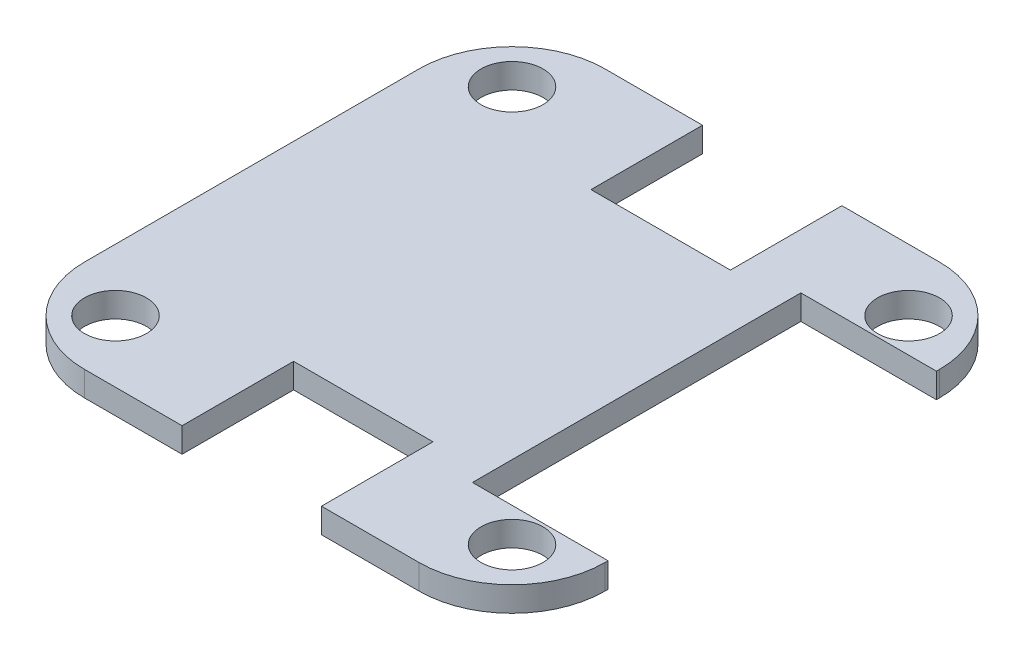
SolidWorks part; units mm, degrees
ref_plane "Front Plane" through (0, 0, 0) normal (0, 0, 1) x (1, 0, 0)
ref_plane "Top Plane" through (0, 0, 0) normal (0, 1, 0) x (1, 0, 0)
ref_plane "Right Plane" through (0, 0, 0) normal (1, 0, 0) x (0, 0, -1)
sketch "Layer1" plane through (0, 0, 0) normal (0, 1, 0) x (1, 0, 0)
  line L0 (11.25, 42) -> (27, 42)
  line L1 (-27, -42) -> (-11.25, -42)
  line L2 (-42, -27) -> (-42, 27)
  line L3 (-27, 42) -> (-11.25, 42)
  line L4 (42, -27) -> (42, 27)
  line L5 (-42, -42) -> (42, 42) construction
  line L6 (-42, 42) -> (42, -42) construction
  line L8 (-11.25, 42) -> (-11.25, 24)
  line L9 (-11.25, 24) -> (11.25, 24)
  line L10 (11.25, 42) -> (11.25, 24)
  line L12 (-11.25, -42) -> (-11.25, -24)
  line L13 (-11.25, -24) -> (11.25, -24)
  line L14 (11.25, -42) -> (11.25, -24)
  line L15 (11.25, -42) -> (27, -42)
  line L18 (-42, -21.5) -> (-42, 21.5)
  arc A0 (27, -42) -> (42, -27) centre (27, -27) ccw
  arc A1 (27, 42) -> (42, 27) centre (27, 27) cw
  arc A2 (-27, -42) -> (-42, -27) centre (-27, -27) cw
  arc A3 (-42, 27) -> (-27, 42) centre (-27, 27) cw
  point P0 (0, 0)
  point P30 (21.7219, 0)
  dimension "D9" = 15
  dimension "D1" = 84
  dimension "D2" = 84
  dimension "D3" = 18
  dimension "D4" = 22.5
  dimension "D5" = 18
  dimension "D6" = 22.5
  dimension "D7" = 30.75
  dimension "D8" = 30.75
  dimension "D10" = 43
extrude "Boss-Extrude1" add sketch "Layer1" along normal blind 4 contours A3 L2 A2 L1 L12 L13 L14 L15 A0 L4 A1 L0 L10 L9 L8 L3 | L2 region at (0, 0, 0)
sketch "Sketch4" plane through (0, 4, 0) normal (0, 1, 0) x (1, 0, 0)
  line L0 (11.25, 42) -> (27, 42) construction
  line L1 (20.12, -26.5) -> (42, -26.5)
  line L2 (20.12, -26.5) -> (20.12, 26.5)
  line L3 (20.12, 26.5) -> (42, 26.5)
  line L4 (42, -26.5) -> (42, 26.5)
  line L5 (20.12, -26.5) -> (42, 26.5) construction
  line L6 (20.12, 26.5) -> (42, -26.5) construction
  line L7 (42, -27) -> (42, 27) construction
  line L8 (-42, -27) -> (-42, 27) construction
  line L13 (-27, 42) -> (-11.25, 42) construction
  line L15 (-7.8, 7.8) -> (7.8, 7.8)
  line L16 (-7.8, 7.8) -> (-7.8, -12.5)
  line L17 (-7.8, -12.5) -> (7.8, -12.5)
  line L18 (7.8, 7.8) -> (7.8, -12.5)
  circle A0 centre (-32, 32) radius 5
  circle A1 centre (32, 32) radius 5
  circle A2 centre (32, -32) radius 5
  circle A3 centre (-32, -32) radius 5
  point P0 (31.06, 0)
  line M15 (42, -27) -> (42, 27)
  dimension "D9" = 10
  dimension "D1" = 53
  dimension "D2" = 21.88
  dimension "D3" = 15.5
  dimension "D4" = 0
  dimension "D10" = 10
  dimension "D11" = 10
  dimension "D5" = 20.3
  dimension "D6" = 15.6
  dimension "D7" = 34.2
  dimension "D8" = 34.2
  dimension "D12" = 2
  dimension "D13" = 2
extrude "Cut-Extrude1" cut sketch "Sketch4" against normal blind 4 contours L3 L2 L1 M15 | A1 | A0 | A3 | A2 region at (31.06, 4, 0) region at (-32, 4, -32) region at (32, 4, -32) region at (32, 4, 32) region at (-32, 4, 32)
equation "\"D6@Layer1\"=\"D4@Layer1\""
equation "\"D5@Layer1\"=\"D3@Layer1\""
equation "\"D2@Layer1\"=\"D1@Layer1\""
equation "\"D7@Layer1\"=(\"D2@Layer1\"-\"D4@Layer1\")/2"
equation "\"D8@Layer1\"=\"D7@Layer1\""
equation "\"D3@Sketch4\"=(\"D1@Layer1\"-\"D1@Sketch4\")/2"
equation "\"D11@Sketch4\"=\"D10@Sketch4\""
equation "\"D7@Sketch4\"=(\"D2@Layer1\"-\"D6@Sketch4\")/2"
equation "\"D8@Sketch4\"=(\"D1@Layer1\"-\"D6@Sketch4\")/2"
